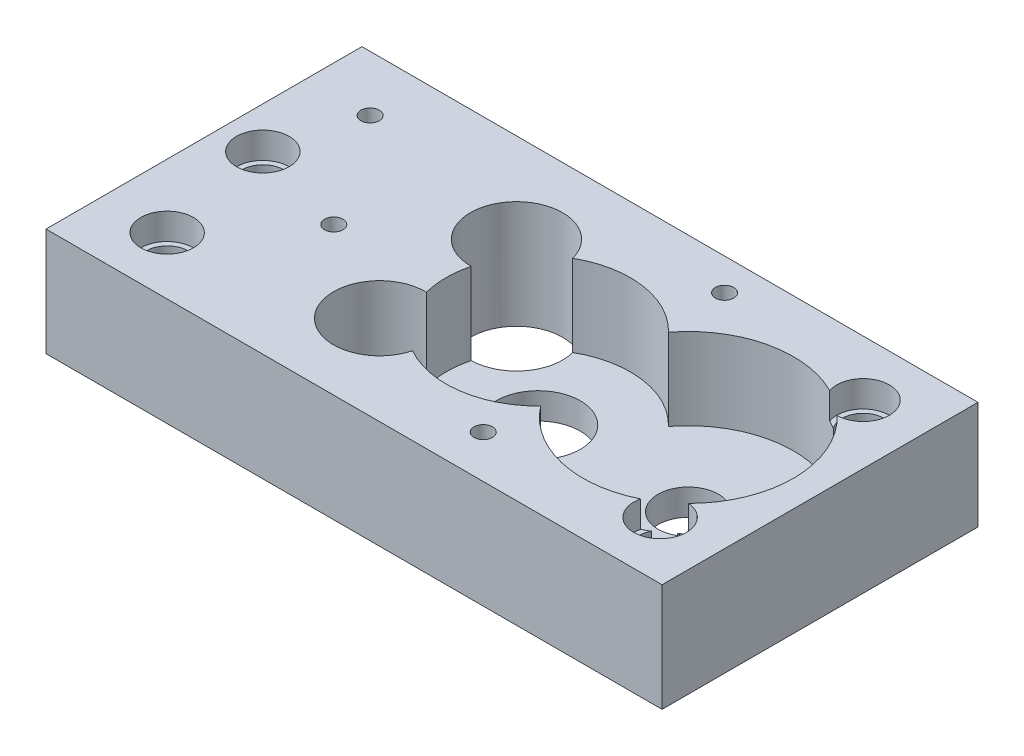
SolidWorks part; units mm, degrees
note: The reader was unsure of these and kept them because the rebuilt part matched: shared geometry of "草图1<4>", "草图3<3>", "草图3<4>".
ref_plane "前视基准面" through (0, 0, 0) normal (0, 0, 1) x (1, 0, 0)
ref_plane "上视基准面" through (0, 0, 0) normal (0, 1, 0) x (1, 0, 0)
ref_plane "右视基准面" through (0, 0, 0) normal (1, 0, 0) x (0, 0, -1)
other "Configuration Table"
sketch "草图1" plane through (0, 0, 0) normal (0, 1, 0) x (1, 0, 0)
  line L1 (0, 0) -> (23.4, 0)
  line L2 (0, 0) -> (0, -12)
  line L3 (0, -12) -> (23.4, -12)
  line L4 (23.4, 0) -> (23.4, -12)
  circle A0 centre (9.2708, -3.4) radius 1.75
  circle A1 centre (18.3957, -6) radius 4
  circle A2 centre (9.2708, -8.6) radius 1.75
  circle A3 centre (12.6957, -6) radius 3.5
  circle A7 centre (12.6957, -6) radius 1.6
  circle A11 centre (18.3957, -6) radius 1.15
  dimension "D3" = 3.5
  dimension "D4" = 2.3
  dimension "D5" = 8
  dimension "D6" = 7
  dimension "D1" = 12
  dimension "D2" = 23.4
extrude "凸台-拉伸1" add sketch "草图1" along normal blind 1 contours L3 L4 L1 L2 | A0 | A7 | A11 | A2
extrude "凸台-拉伸2" add sketch "草图1<4>" along normal blind 3.1 from surface at 1 contours L3 L4 L1 L2 | A2 | A0 | A1 | A3
sketch "草图1<4>" plane through (0, 0, 0) normal (0, 1, 0) x (1, 0, 0) same geometry as "草图1"
sketch "草图3" plane through (0, 4.1, 0) normal (0, 1, 0) x (1, 0, 0)
  circle A0 centre (1.5689, -5.3325) radius 0.8
  circle A1 centre (1.5689, -5.3325) radius 1
  circle A2 centre (21.1432, -2.1089) radius 0.8
  circle A3 centre (2.4192, -9.8175) radius 0.8
  circle A4 centre (2.4192, -9.8175) radius 1
  circle A5 centre (21.1432, -2.1089) radius 1
  circle A6 centre (21.1432, -9.8175) radius 0.8
  circle A7 centre (21.1432, -9.8175) radius 1
  circle A8 centre (2.4192, -2.1089) radius 0.35
  circle A9 centre (14.9835, -1.2099) radius 0.35
  circle A10 centre (14.9835, -10.3761) radius 0.35
  circle A11 centre (5.3147, -6.3844) radius 0.35
  dimension "D1" = 2
  dimension "D2" = 1.6
  dimension "D3" = 0.7
extrude "切除-拉伸3" cut sketch "草图3" against normal blind 2 contours A8 | A11 | A9 | A10
extrude "切除-拉伸4" cut sketch "草图3<3>" against normal blind 1 contours A1 | A4 | A7 | A5
sketch "草图3<3>" plane through (0, 4.1, 0) normal (0, 1, 0) x (1, 0, 0) same geometry as "草图3"
extrude "切除-拉伸5" cut sketch "草图3<4>" against normal through all contours A0 | A3 | A6 | A2
sketch "草图3<4>" plane through (0, 4.1, 0) normal (0, 1, 0) x (1, 0, 0) same geometry as "草图3"
